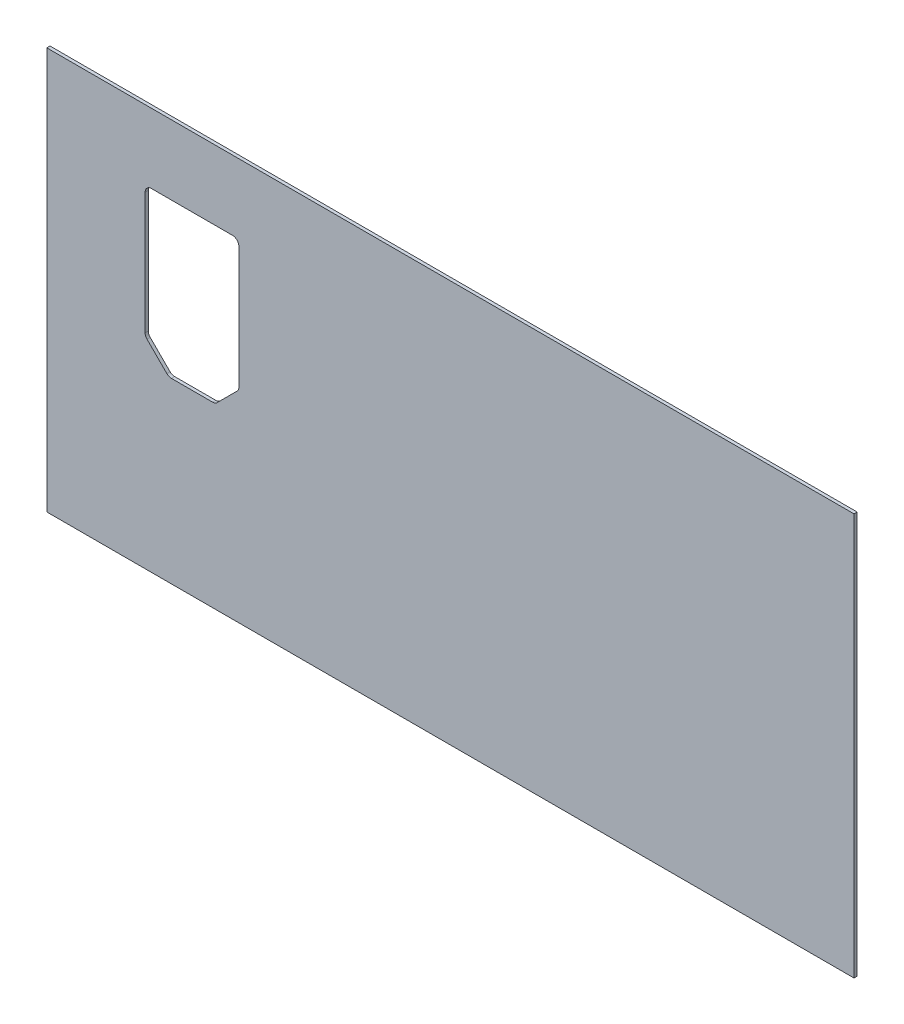
SolidWorks part; units mm, degrees
ref_plane "Front Plane" through (0, 0, 0) normal (0, 0, 1) x (1, 0, 0)
ref_plane "Top Plane" through (0, 0, 0) normal (0, 1, 0) x (1, 0, 0)
ref_plane "Right Plane" through (0, 0, 0) normal (1, 0, 0) x (0, 0, -1)
sketch "Sketch1" plane through (0, 0, 0) normal (0, 0, 1) x (1, 0, 0)
  line L0 (-67, 19.75) -> (-66.3, 19.75) construction
  line L1 (-126.5, 63) -> (126.5, 63)
  line L2 (-126.5, 63) -> (-126.5, -63)
  line L3 (-126.5, -63) -> (126.5, -63)
  line L4 (126.5, 63) -> (126.5, -63)
  line L5 (0, -63) -> (0, 63) construction
  line L6 (-126.5, 0) -> (126.5, 0) construction
  line L7 (-67, 39) -> (-67, 0.5) construction
  line L8 (-81, 40.5) -> (-81, 41.2) construction
  line L9 (-93.5, 40.5) -> (-68.5, 40.5) construction
  line L10 (-70.5, -3) -> (-70.005, -3.495) construction
  line L11 (-67, 0.5) -> (-74, -6.5) construction
  line L12 (-81, -6.5) -> (-81, -7.2) construction
  line L13 (-74, -6.5) -> (-88, -6.5) construction
  line L14 (-95, 19.75) -> (-95.7, 19.75) construction
  line L15 (-95, 0.5) -> (-95, 39) construction
  line L16 (-91.5, -3) -> (-91.995, -3.495) construction
  line L17 (-88, -6.5) -> (-95, 0.5) construction
  line L24 (-81, -7.2) -> (-74.5385, -7.2)
  line L26 (-91.995, -3.495) -> (-88.8757, -6.6142)
  line L27 (-81, -7.2) -> (-87.4615, -7.2)
  line L28 (-91.995, -3.495) -> (-94.0649, -1.425)
  line L29 (-95.7, 19.75) -> (-95.7, 1.0385)
  line L30 (-95.7, 19.75) -> (-95.7, 39.2)
  line L31 (-93.7, 41.2) -> (-68.3, 41.2)
  line L32 (-66.3, 39.2) -> (-66.3, 1.0385)
  line L33 (-70.005, -3.495) -> (-66.8858, -0.3757)
  line L34 (-94.0649, -1.425) -> (-95.1142, -0.3757)
  line L35 (-70.005, -3.495) -> (-73.1243, -6.6142)
  arc A0 (-66.3, 1.0385) -> (-66.8858, -0.3757) centre (-68.3, 1.0385) cw
  arc A1 (-74.5385, -7.2) -> (-73.1243, -6.6142) centre (-74.5385, -5.2) ccw
  arc A2 (-88.8757, -6.6142) -> (-87.4615, -7.2) centre (-87.4615, -5.2) ccw
  arc A3 (-95.1142, -0.3757) -> (-95.7, 1.0385) centre (-93.7, 1.0385) cw
  arc A4 (-95.7, 39.2) -> (-93.7, 41.2) centre (-93.7, 39.2) cw
  arc A5 (-68.3, 41.2) -> (-66.3, 39.2) centre (-68.3, 39.2) cw
  point P0 (0, 0)
  dimension "D9" = 2
  dimension "D1" = 126
  dimension "D2" = 253
  dimension "D3" = 0.7
  dimension "D4" = 0.7
  dimension "D5" = 0.7
  dimension "D6" = 0.7
  dimension "D7" = 0.7
  dimension "D8" = 0.7
base flange "Base-Flange1" sketch "Sketch1" thickness 1 reverse thickness direction no parameters "D1"=0.7366
sketch "Sketch2" plane through (0, 0, -1) normal (0, 0, -1) x (-1, 0, 0)
  line L0 (0, 63) -> (0, -63) construction
  line L1 (-126.5, 63) -> (126.5, 63) construction
  line L2 (126.5, -63) -> (-126.5, -63) construction
  line L3 (-126.5, 0) -> (126.5, 0) construction
  line L4 (-126.5, -63) -> (-126.5, 63) construction
  line L5 (126.5, 63) -> (126.5, -63) construction
sketch "Bend-Lines1" [suppressed] plane through (0, 0, 0) normal (0, 1, 0) x (1, 0, 0)
sketch "Bounding-Box1" [suppressed] plane through (0, 0, 0) normal (0, 1, 0) x (1, 0, 0)
sheet metal parameters "Sheet-Metal1" thickness 1 parameters "D1"=0.7366
flat pattern "Flat-Pattern1" [suppressed]
sketch "Bend-Lines2" plane through (0, 0, 0) normal (0, 1, 0) x (1, 0, 0)
sketch3d "Bounding-Box2" [suppressed]
  line L0 (126.5, -63, 0) -> (-126.5, -63, 0) construction
  line L1 (126.5, 63, 0) -> (-126.5, 63, 0) construction
  line L2 (126.5, -63, 0) -> (126.5, 63, 0) construction
  line L3 (-126.5, -63, 0) -> (-126.5, 63, 0) construction
